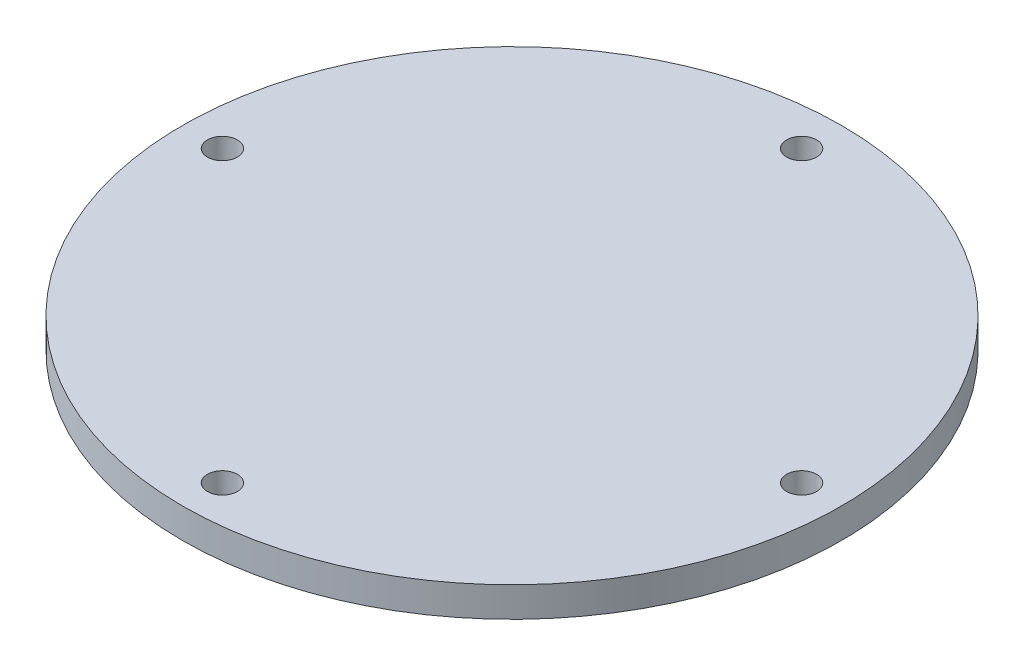
SolidWorks part; units mm, degrees
ref_plane "Front Plane" through (0, 0, 0) normal (0, 0, 1) x (1, 0, 0)
ref_plane "Top Plane" through (0, 0, 0) normal (0, 1, 0) x (1, 0, 0)
ref_plane "Right Plane" through (0, 0, 0) normal (1, 0, 0) x (0, 0, -1)
sketch "Sketch1" plane through (0, 0, 0) normal (0, 1, 0) x (1, 0, 0)
  circle A0 centre (0, 0) radius 33
  circle A1 centre (-29, 0) radius 1.5
  circle A2 centre (0, 0) radius 29 construction
  circle A3 centre (0, 29) radius 1.5
  circle A4 centre (29, 0) radius 1.5
  circle A5 centre (0, -29) radius 1.5
  point P15 (0, 0)
  dimension "D1" = 66
  dimension "D2" = 4
  dimension "D3" = 3
  dimension "D4" = 4
extrude "Boss-Extrude1" add sketch "Sketch1" along normal blind 3
